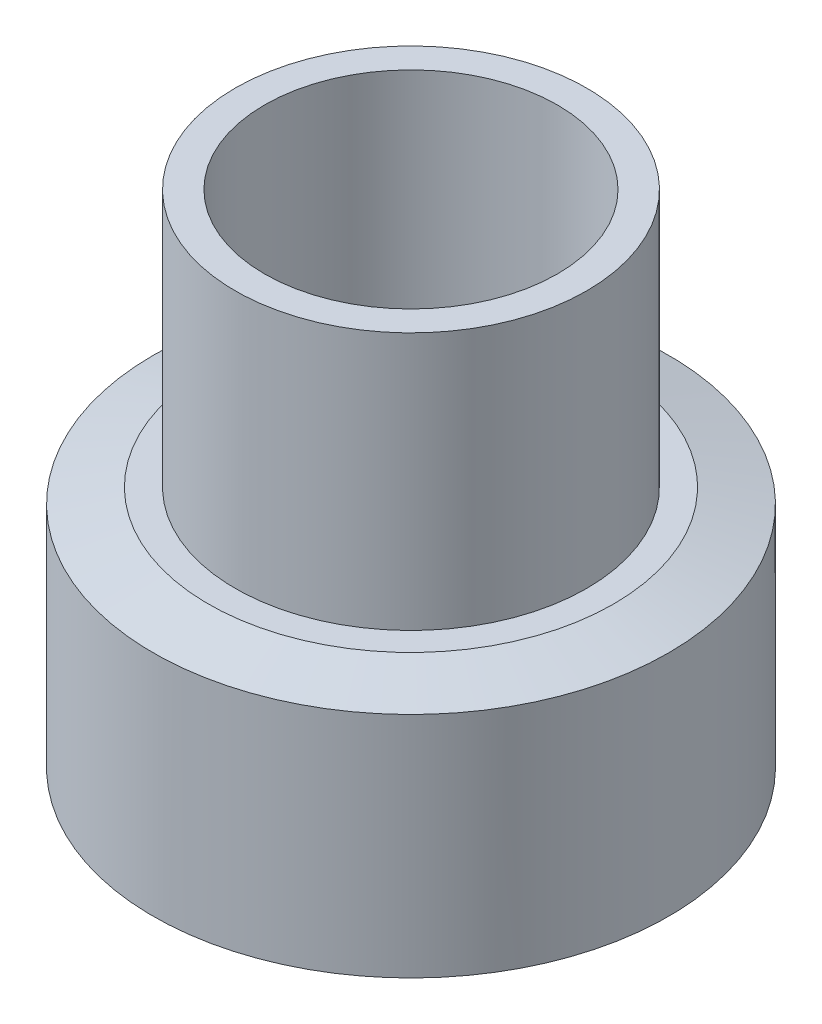
SolidWorks part; units mm, degrees
material "Сталь ШХ15 ГОСТ 801-78"
ref_plane "Plane1" through (0, 0, 0) normal (0, 0, 1) x (1, 0, 0)
ref_plane "Plane2" through (0, 0, 0) normal (0, 1, 0) x (1, 0, 0)
ref_plane "Plane3" through (0, 0, 0) normal (1, 0, 0) x (0, 0, -1)
sketch "Эскиз2" plane through (0, 0, 0) normal (0, 0, 1) x (1, 0, 0)
  line L0 (0, 0) -> (4.4, 0)
  line L1 (4.4, 0) -> (4.4, 4.4)
  line L2 (4.4, 4.4) -> (3, 4.4)
  line L3 (3, 4.4) -> (3, 8.8)
  line L4 (3, 8.8) -> (0, 8.8)
  line L5 (0, 8.8) -> (0, 0)
  dimension "D1" = 4.4
  dimension "D2" = 4.4
  dimension "D3" = 4.4
  dimension "3" = 3
ref_axis "Ось1" through (0, 8.8, 0) along (0, -1, 0)
revolve "Повернуть2" add sketch "Эскиз2" angle 360 about axis through (0, 8.8, 0) along (0, -1, 0)
chamfer "Фаска2" distance 0.94 angle 15 1 edges at (-4.4, 4.4, 0) first distance on face at (-3, 4.4, 0)
chamfer "Фаска3" distance 0.94 angle 15 1 edges at (-4.4, 0, 0) first distance on face at (-4.4, 0, 0)
sketch "Эскиз4" plane through (0, 8.8, 0) normal (0, 1, 0) x (1, 0, 0)
  circle A0 centre (0, 0) radius 2.5
  dimension "D1" = 5
extrude "Вырез-Вытянуть2" cut sketch "Эскиз4" against normal through all both contours A0
